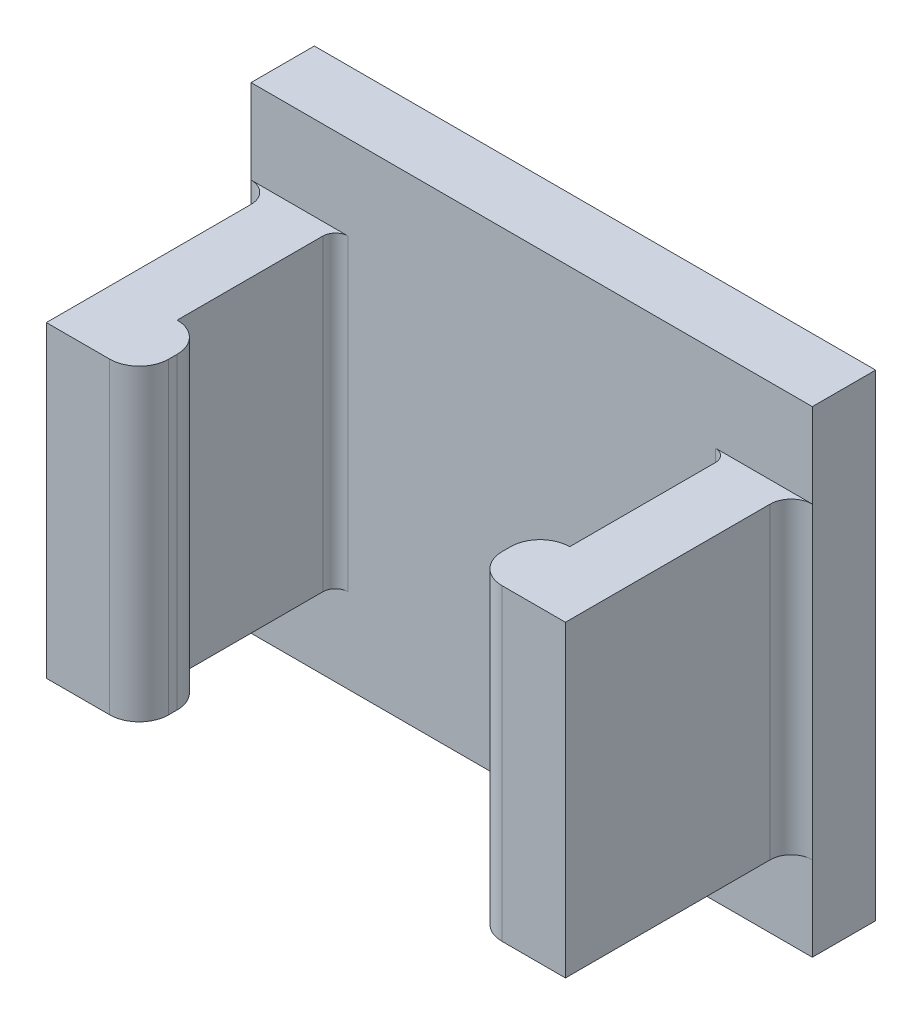
SolidWorks part; units mm, degrees
ref_plane "정면" through (0, 0, 0) normal (0, 0, 1) x (1, 0, 0)
ref_plane "윗면" through (0, 0, 0) normal (0, 1, 0) x (1, 0, 0)
ref_plane "우측면" through (0, 0, 0) normal (1, 0, 0) x (0, 0, -1)
sketch "스케치1" plane through (0, 0, 0) normal (0, 0, 1) x (1, 0, 0)
  line L1 (-6.15, -5.65) -> (6.15, -5.65)
  line L2 (-6.15, -5.65) -> (-6.15, 5.65)
  line L3 (-6.15, 5.65) -> (6.15, 5.65)
  line L4 (6.15, -5.65) -> (6.15, 5.65)
  line L5 (-6.15, -5.65) -> (6.15, 5.65) construction
  line L6 (-6.15, 5.65) -> (6.15, -5.65) construction
  point P0 (0, 0)
  dimension "D1" = 12.3
  dimension "D2" = 11.3
extrude "보스-돌출1" add sketch "스케치1" along normal blind 2.5
sketch "스케치2" plane through (0, 0, 2.5) normal (0, 0, 1) x (1, 0, 0)
  line L0 (-6.15, -5.65) -> (6.15, -5.65) construction
  line L1 (-6.15, 5.65) -> (-4.65, 5.65)
  line L2 (-6.15, 5.65) -> (-6.15, -5.65)
  line L3 (-6.15, -5.65) -> (-4.65, -5.65)
  line L4 (-4.65, 5.65) -> (-4.65, -5.65)
  line L6 (6.15, 5.65) -> (4.65, 5.65)
  line L7 (6.15, 5.65) -> (6.15, -5.65)
  line L8 (6.15, -5.65) -> (4.65, -5.65)
  line L9 (4.65, 5.65) -> (4.65, -5.65)
  dimension "D1" = 1.5
  dimension "D2" = 1.5
extrude "보스-돌출2" add sketch "스케치2" along normal blind 4.35
sketch "스케치5" plane through (0, 0, 2.5) normal (0, 0, 1) x (1, 0, 0)
  line L0 (4.65, 5.65) -> (4.65, -5.65) construction
  line L1 (-4.65, -5.75) -> (4.65, -5.75)
  line L2 (-4.65, -5.75) -> (-4.65, 5.75)
  line L3 (-4.65, 5.75) -> (4.65, 5.75)
  line L4 (4.65, -5.75) -> (4.65, 5.75)
  line L5 (-4.65, -5.75) -> (4.65, 5.75) construction
  line L6 (-4.65, 5.75) -> (4.65, -5.75) construction
  point P0 (0, 0)
  dimension "D1" = 11.5
extrude "컷-돌출1" cut sketch "스케치5" against normal blind 1
sketch "스케치8" plane through (-4.65, 0, 0) normal (1, 0, 0) x (0, 0, -1)
  line L0 (-6.85, -5.65) -> (-1.5, -5.65) construction
  line L1 (-6.85, 5.65) -> (-5.25, 5.65)
  line L2 (-6.85, 5.65) -> (-6.85, -5.65)
  line L3 (-6.85, -5.65) -> (-5.25, -5.65)
  line L4 (-5.25, 5.65) -> (-5.25, -5.65)
  dimension "D1" = 1.6
extrude "보스-돌출5" add sketch "스케치8" along normal blind 0.7
sketch "스케치9" plane through (4.65, 0, 0) normal (-1, 0, 0) x (0, 0, 1)
  line L0 (6.85, 5.65) -> (1.5, 5.65) construction
  line L1 (6.85, -5.65) -> (5.25, -5.65)
  line L2 (6.85, -5.65) -> (6.85, 5.65)
  line L3 (6.85, 5.65) -> (5.25, 5.65)
  line L4 (5.25, -5.65) -> (5.25, 5.65)
  dimension "D1" = 1.6
extrude "보스-돌출6" add sketch "스케치9" along normal blind 0.7
fillet "필렛8" radius 0.3 2 edges at (4.65, 0, 1.5) (-4.65, 0, 1.5)
sketch "스케치11" plane through (0, 5.65, 0) normal (0, 1, 0) x (1, 0, 0)
  line L0 (6.15, -6.85) -> (6.15, 0) construction
  line L1 (-6.15, -6.85) -> (6.15, -6.85)
  line L2 (-6.15, -6.85) -> (-6.15, -1.5)
  line L3 (-6.15, -1.5) -> (6.15, -1.5)
  line L4 (6.15, -6.85) -> (6.15, -1.5)
  line L5 (-4.35, -1.5) -> (4.35, -1.5) construction
  dimension "D1" = 0
extrude "컷-돌출2" cut sketch "스케치11" against normal blind 2
sketch "스케치12" plane through (0, -5.65, 0) normal (0, -1, 0) x (1, 0, 0)
  line L0 (6.15, 6.85) -> (6.15, 0) construction
  line L1 (-6.15, 6.85) -> (6.15, 6.85)
  line L2 (-6.15, 6.85) -> (-6.15, 1.5)
  line L3 (-6.15, 1.5) -> (6.15, 1.5)
  line L4 (6.15, 6.85) -> (6.15, 1.5)
  line L5 (4.35, 1.5) -> (-4.35, 1.5) construction
  dimension "D1" = 0
extrude "컷-돌출3" cut sketch "스케치12" against normal blind 2
sketch "스케치13" plane through (6.15, 0, 0) normal (1, 0, 0) x (0, 0, -1)
  line L1 (-1.5, 5.65) -> (0, 5.65)
  line L2 (-1.5, 5.65) -> (-1.5, -5.65)
  line L3 (-1.5, -5.65) -> (0, -5.65)
  line L4 (0, 5.65) -> (0, -5.65)
extrude "보스-돌출7" add sketch "스케치13" along normal blind 0.5
sketch "스케치14" plane through (-6.15, 0, 0) normal (-1, 0, 0) x (0, 0, 1)
  line L1 (1.5, 5.65) -> (0, 5.65)
  line L2 (1.5, 5.65) -> (1.5, -5.65)
  line L3 (1.5, -5.65) -> (0, -5.65)
  line L4 (0, 5.65) -> (0, -5.65)
extrude "보스-돌출8" add sketch "스케치14" along normal blind 0.5
fillet "필렛9" radius 0.5 2 edges at (6.15, 0, 1.5) (-6.15, 0, 1.5)
fillet "필렛10" radius 0.7 4 edges at (-3.95, 0, 6.85) (-3.95, 0, 5.25) (3.95, 0, 5.25) (3.95, 0, 6.85)
